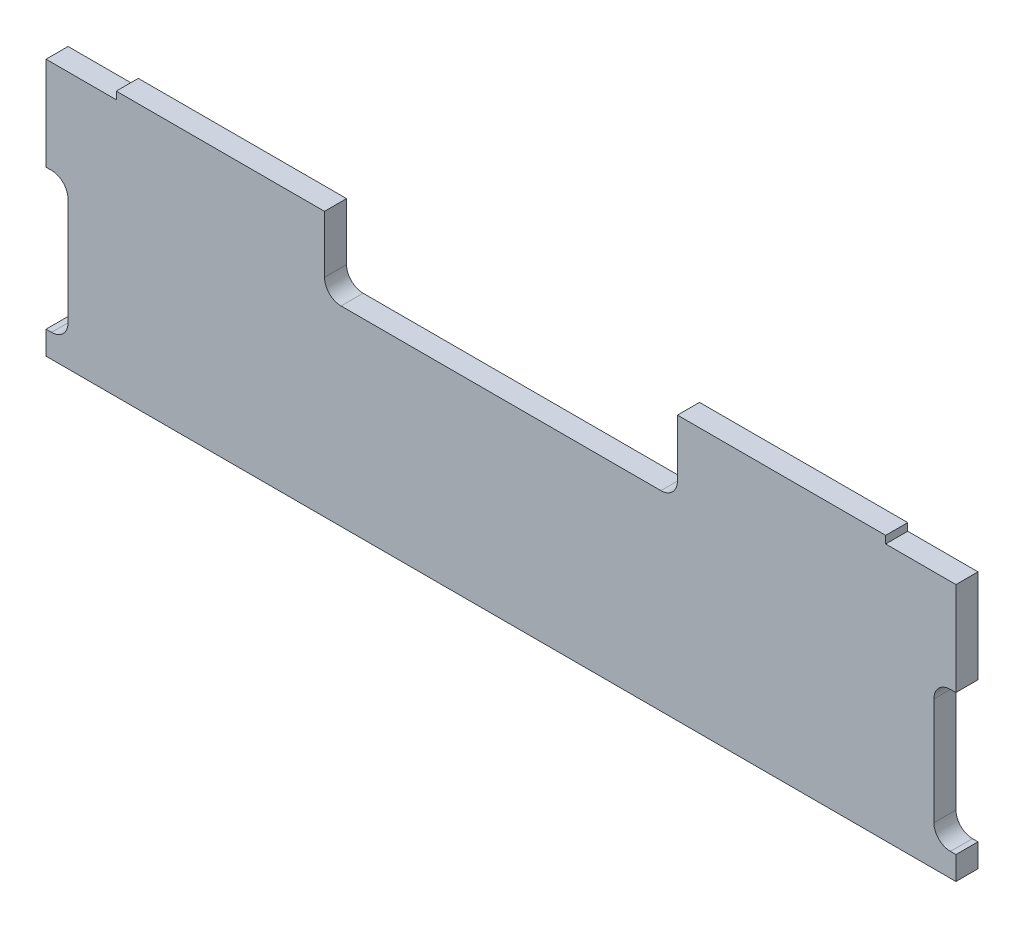
SolidWorks part; units mm, degrees
material "Alloy Steel"
ref_plane "Front Plane" through (0, 0, 0) normal (0, 0, 1) x (1, 0, 0)
ref_plane "Top Plane" through (0, 0, 0) normal (0, 1, 0) x (1, 0, 0)
ref_plane "Right Plane" through (0, 0, 0) normal (1, 0, 0) x (0, 0, -1)
sketch "Sketch1" plane through (0, 0, 0) normal (0, 0, 1) x (1, 0, 0)
  line L1 (130.9687, 34.925) -> (-130.9688, 34.925)
  line L2 (130.9687, 34.925) -> (130.9687, -34.925)
  line L3 (130.9687, -34.925) -> (-130.9688, -34.925)
  line L4 (-130.9688, 34.925) -> (-130.9688, -34.925)
  line L5 (130.9687, 34.925) -> (-130.9688, -34.925) construction
  line L6 (130.9687, -34.925) -> (-130.9688, 34.925) construction
  point P0 (0, 0)
  dimension "D1" = 261.9375
  dimension "D2" = 69.85
extrude "Boss-Extrude1" add sketch "Sketch1" along normal blind 6.35
sketch "Sketch2" plane through (0, 0, 6.35) normal (0, 0, 1) x (1, 0, 0)
  line L0 (-130.9688, 34.925) -> (-130.9688, -34.925) construction
  line L1 (-130.9688, 9.525) -> (-124.6188, 9.525)
  line L2 (-130.9688, 9.525) -> (-130.9688, -28.575)
  line L3 (-130.9688, -28.575) -> (-124.6188, -28.575)
  line L4 (-124.6188, 9.525) -> (-124.6188, -28.575)
  line L5 (-130.9688, -34.925) -> (130.9687, -34.925) construction
  line L6 (130.9687, 34.925) -> (-130.9688, 34.925) construction
  line L7 (0, 34.925) -> (0, -34.925) construction
  line L8 (130.9688, -28.575) -> (124.6188, -28.575)
  line L9 (130.9688, 9.525) -> (130.9688, -28.575)
  line L10 (130.9688, 9.525) -> (124.6188, 9.525)
  line L11 (124.6188, 9.525) -> (124.6188, -28.575)
  dimension "D1" = 6.35
  dimension "D2" = 6.35
  dimension "D3" = 25.4
extrude "Cut-Extrude1" cut sketch "Sketch2" against normal through all
scale "Scale1" scale about centroid uniform scaling no x scale factor 1 y scale factor 1.06 z scale factor 1
sketch "Sketch3" plane through (0, 0, 6.35) normal (0, 0, 1) x (1, 0, 0)
  line L0 (0, 37.005) -> (0, -37.036) construction
  line L1 (130.9687, 37.005) -> (-130.9688, 37.005) construction
  line L2 (-130.9688, -37.036) -> (130.9687, -37.036) construction
  line L4 (-50.8, 37.005) -> (50.8, 37.005)
  line L5 (-50.8, 37.005) -> (-50.8, 17.955)
  line L6 (-50.8, 17.955) -> (50.8, 17.955)
  line L7 (50.8, 37.005) -> (50.8, 17.955)
  dimension "D1" = 19.05
  dimension "D2" = 101.6
extrude "Cut-Extrude2" cut sketch "Sketch3" against normal through all
fillet "Fillet1" radius 4.7625 6 edges at (50.8, 17.955, 3.175) (-50.8, 17.955, 3.175) (124.6188, -30.305, 3.175) (124.6188, 10.081, 3.175) (-124.6188, -30.305, 3.175) (-124.6188, 10.081, 3.175)
sketch "Sketch4" plane through (0, 0, 6.35) normal (0, 0, 1) x (1, 0, 0)
  line L0 (-50.8, 37.005) -> (-130.9688, 37.005) construction
  line L1 (-110.744, 37.005) -> (-50.8, 37.005)
  line L2 (-110.744, 37.005) -> (-110.744, 39.164)
  line L3 (-110.744, 39.164) -> (-50.8, 39.164)
  line L4 (-50.8, 37.005) -> (-50.8, 39.164)
  line L5 (-50.8, 37.005) -> (-50.8, 22.7175) construction
  line L6 (0, 0) -> (0, 17.955) construction
  line L7 (-46.0375, 17.955) -> (46.0375, 17.955) construction
  line L8 (50.8, 37.005) -> (50.8, 39.164)
  line L9 (110.744, 39.164) -> (50.8, 39.164)
  line L10 (110.744, 37.005) -> (110.744, 39.164)
  line L11 (110.744, 37.005) -> (50.8, 37.005)
  dimension "D1" = 59.944
  dimension "D2" = 2.159
extrude "Boss-Extrude2" add sketch "Sketch4" against normal up to surface (6.35 mm away) up to face at (0, 1.4534, 0)
